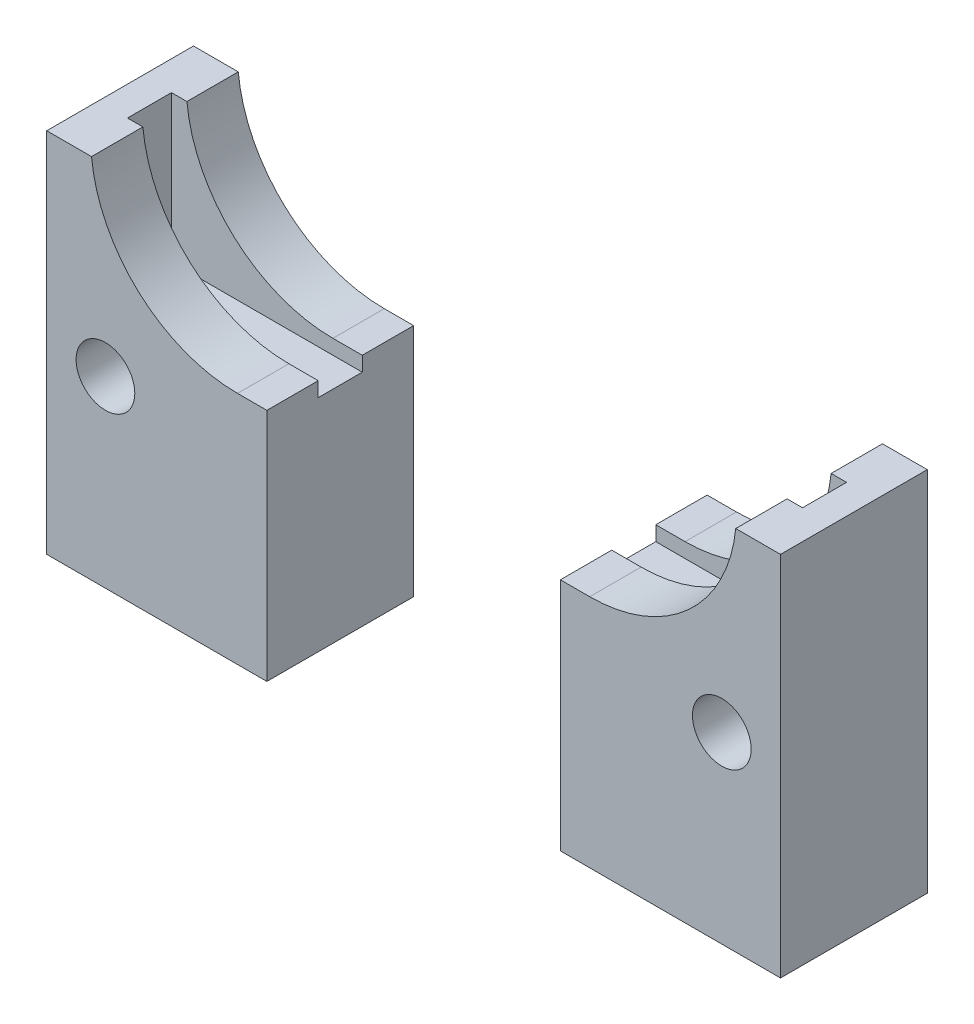
SolidWorks part; units mm, degrees
material "ABS"
ref_plane "Front" through (0, 0, 0) normal (0, 0, 1) x (1, 0, 0)
ref_plane "Top" through (0, 0, 0) normal (0, 1, 0) x (1, 0, 0)
ref_plane "Right" through (0, 0, 0) normal (1, 0, 0) x (0, 0, -1)
sketch "Sketch1" plane through (0, 0, 0) normal (0, 1, 0) x (1, 0, 0)
  line L1 (-25, -5) -> (25, -5)
  line L2 (-25, -5) -> (-25, 5)
  line L3 (-25, 5) -> (25, 5)
  line L4 (25, -5) -> (25, 5)
  line L5 (-25, -5) -> (25, 5) construction
  line L6 (-25, 5) -> (25, -5) construction
  point P0 (0, 0)
  dimension "D1" = 10
  dimension "D2" = 50
extrude "Boss-Extrude1" add sketch "Sketch1" along normal blind 15
sketch "Sketch3" plane through (0, 15, 0) normal (0, 1, 0) x (1, 0, 0)
  line L1 (-23, 1.5) -> (23, 1.5)
  line L2 (-23, 1.5) -> (-23, -1.5)
  line L3 (-23, -1.5) -> (23, -1.5)
  line L4 (23, 1.5) -> (23, -1.5)
  line L5 (-23, 1.5) -> (23, -1.5) construction
  line L6 (-23, -1.5) -> (23, 1.5) construction
  point P0 (0, 0)
  dimension "D1" = 46
  dimension "D2" = 3
extrude "Cut-Extrude1" cut sketch "Sketch3" against normal blind 10
sketch "Sketch4" plane through (0, 0, 5) normal (0, 0, 1) x (1, 0, 0)
  line L0 (0, 0) -> (-23, 0) construction
  line L1 (-25, 0) -> (25, 0) construction
  line L2 (0, 0) -> (23, 0) construction
  line L3 (-10, 0) -> (-10, 6)
  line L4 (0, 0) -> (0, 15)
  line L5 (-25, 15) -> (25, 15) construction
  line L6 (-10, 6) -> (-12, 6)
  line L7 (-22, 16) -> (-22, 15)
  line L8 (-22, 15) -> (22, 15)
  line L9 (-10, 0) -> (10, 0)
  line L10 (10, 0) -> (10, 6)
  line L11 (10, 6) -> (12, 6)
  line L12 (22, 16) -> (22, 15)
  line L13 (10, 0) -> (10, 6)
  line L14 (10, 6) -> (12, 6)
  line L15 (22, 16) -> (22, 15)
  arc A0 (-12, 6) -> (-22, 16) centre (-12, 16) cw
  arc A1 (12, 6) -> (22, 16) centre (12, 16) ccw
  point P19 (-22, 6)
  line M3 (-25, 0) -> (25, 0)
  line M5 (25, 15) -> (-25, 15)
  dimension "D5" = 10
  dimension "D1" = 23
  dimension "D2" = 23
  dimension "D3" = 6
  dimension "D4" = 10
  dimension "6" = 12
extrude "Cut-Extrude2" cut sketch "Sketch4" against normal blind 10 contours L7 L6 L3 L4 M3 M5 | L11 L12 L4 L10 M5 M3 region at (-8.6837, 8.8036, 5) region at (8.6837, 8.8036, 5)
sketch "Sketch5" plane through (0, 0, 0) normal (0, -1, 0) x (1, 0, 0)
  line L0 (25, 5) -> (25, -5) construction
  line L1 (-25, -5) -> (-10, -5)
  line L2 (-25, -5) -> (-25, 5)
  line L3 (-25, 5) -> (-10, 5)
  line L4 (-10, -5) -> (-10, 5)
  line L5 (10, -5) -> (25, -5)
  line L6 (10, -5) -> (10, 5)
  line L7 (10, 5) -> (25, 5)
  line L8 (25, -5) -> (25, 5)
extrude "Boss-Extrude2" add sketch "Sketch5" along normal blind 10
sketch "Sketch6" plane through (0, 0, 5) normal (0, 0, 1) x (1, 0, 0)
  line L0 (-21, 2.5) -> (21, 2.5) construction
  line L1 (-25, 15) -> (-25, -10) construction
  line L3 (25, 15) -> (25, -10) construction
  line L5 (-10, 0) -> (10, 0) construction
  circle A0 centre (-21, 2.5) radius 2
  circle A1 centre (21, 2.5) radius 2
  dimension "D1" = 4
  dimension "D2" = 4
  dimension "D3" = 2.5
  dimension "D4" = 4
extrude "Cut-Extrude3" cut sketch "Sketch6" against normal through all
